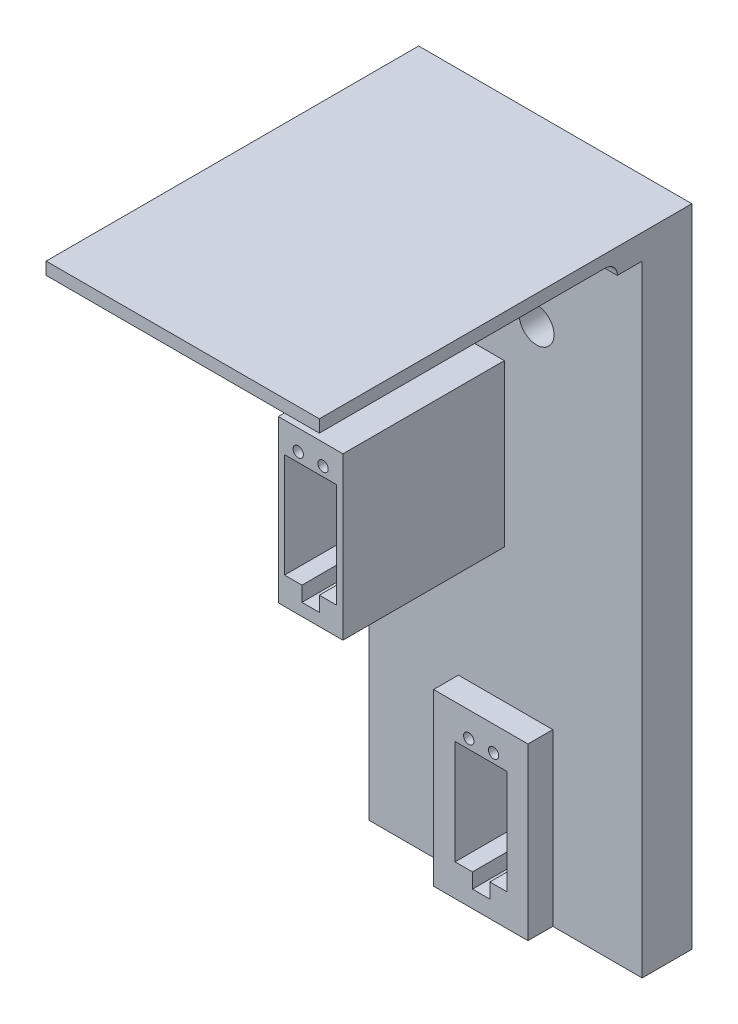
SolidWorks part; units mm, degrees
ref_plane "Front Plane" through (0, 0, 0) normal (0, 0, 1) x (1, 0, 0)
ref_plane "Top Plane" through (0, 0, 0) normal (0, 1, 0) x (1, 0, 0)
ref_plane "Right Plane" through (0, 0, 0) normal (1, 0, 0) x (0, 0, -1)
sketch "Sketch1" plane through (0, 0, 0) normal (0, 0, 1) x (1, 0, 0)
  line L1 (-75, 100) -> (75, 100)
  line L2 (-75, 100) -> (-75, -100)
  line L3 (-75, -100) -> (75, -100)
  line L4 (75, 100) -> (75, -100)
  line L5 (-75, 100) -> (75, -100) construction
  line L6 (-75, -100) -> (75, 100) construction
  point P0 (0, 0)
  dimension "D1" = 200
  dimension "D2" = 150
extrude "Boss-Extrude1" add sketch "Sketch1" along normal blind 30
sketch "Sketch2" plane through (0, 0, 30) normal (0, 0, 1) x (1, 0, 0)
  line L0 (75, -100) -> (75, 100) construction
  line L1 (-75, 100) -> (75, 100)
  line L2 (-75, 100) -> (-75, 95)
  line L3 (-75, 95) -> (75, 95)
  line L4 (75, 100) -> (75, 95)
  dimension "D1" = 5
extrude "Boss-Extrude2" add sketch "Sketch2" along normal blind 120
sketch "Sketch3" plane through (0, 0, 30) normal (0, 0, 1) x (1, 0, 0)
  line L0 (0, -100) -> (0, 0)
  line L1 (-75, -100) -> (75, -100) construction
  line L4 (0, 46.5) -> (0, 71.5)
  line L9 (-10.3251, 73.9819) -> (12.4051, 43.2014) construction
  line L10 (-12.4051, 43.2014) -> (10.3251, 73.9819) construction
  line L11 (-39.5, 13) -> (-39.5, 7)
  line L25 (-43, 13) -> (-36, 7) construction
  line L26 (-43, 7) -> (-36, 13) construction
  line L27 (-15.8, 46.5) -> (-12.5, 46.5)
  line L28 (-12.5, 46.5) -> (12.5, 46.5)
  line L29 (-12.5, 59) -> (12.5, 59)
  line L30 (12.5, 46.5) -> (-12.5, 46.5)
  line L31 (12.5, 46.5) -> (12.5, 71.5)
  line L32 (12.5, 71.5) -> (-12.5, 71.5)
  line L33 (-12.5, 46.5) -> (-12.5, 71.5)
  circle A0 centre (12.5, 46.5) radius 1.65
  circle A1 centre (-12.5, 46.5) radius 1.65
  circle A2 centre (12.5, 71.5) radius 1.65
  circle A3 centre (-12.5, 71.5) radius 1.65
  circle A4 centre (-12.5, 71.5) radius 3.3
  circle A5 centre (12.5, 71.5) radius 3.3
  circle A6 centre (12.5, 46.5) radius 3.3
  circle A7 centre (-12.5, 46.5) radius 3.3
  point P5 (0, 60)
  point P22 (-39.5, 10)
  dimension "D13" = 3.3
  dimension "D14" = 6.6
  dimension "D7" = 6
  dimension "D8" = 7
  dimension "D11" = 25
  dimension "D12" = 25
extrude "Cut-Extrude3" cut sketch "Sketch3" against normal blind 80 contours L11 | L11 | A1 L27 L33 | A1 L28 L27 | A1 L33 L28 | L31 A0 L30 | L30 A0 L31 | A2 L32 L31 | A2 L31 L32 | L32 A3 L33 | L33 A3 L32 region at (-12.5, 45.7997, 30) region at (-11.7997, 47.2003, 30) region at (11.7997, 47.2003, 30) region at (12.7334, 46.2666, 30) region at (-13.2003, 47.2003, 30) region at (-11.7997, 70.7997, 30) region at (-12.7334, 71.7334, 30) region at (12.7334, 71.7334, 30) region at (11.7997, 70.7997, 30)
ref_plane "Plane1" through (0, 0, 30) normal (0, 0, 1) x (1, 0, 0)
sketch "Sketch6" plane through (0, 0, 30) normal (0, 0, 1) x (1, 0, 0)
  circle A0 centre (-12.5, 71.5) radius 5
  circle A1 centre (12.5, 71.5) radius 5
  circle A2 centre (-12.5, 46.5) radius 5
  circle A3 centre (12.5, 46.5) radius 5
  dimension "D1" = 10
  dimension "D2" = 10
  dimension "D3" = 10
  dimension "D4" = 10
extrude "Cut-Extrude5" cut sketch "Sketch6" against normal blind 22
sketch "Sketch7" plane through (0, 0, 8) normal (0, 0, 1) x (1, 0, 0)
  circle A0 centre (-12.5, 71.5) radius 1.925
  circle A1 centre (12.5, 71.5) radius 1.925
  circle A2 centre (-12.5, 46.5) radius 1.925
  circle A3 centre (12.5, 46.5) radius 1.925
  dimension "D1" = 3.85
  dimension "D2" = 3.85
  dimension "D3" = 3.85
  dimension "D4" = 3.85
extrude "Cut-Extrude6" cut sketch "Sketch7" against normal blind 5
sketch "Sketch9" plane through (0, 0, 30) normal (0, 0, 1) x (1, 0, 0)
  line L0 (-12.5, 46.5) -> (12.5, 46.5)
  line L1 (12.5, 46.5) -> (0, 46.5)
  line L2 (0, 46.5) -> (1.1812, -69.9316)
  line L3 (1.1812, -69.9316) -> (1.1812, -115.5276)
  line L4 (-13.5, 15.5) -> (0.3145, 15.5)
  line L5 (-2.604, -89.8179) -> (4.396, -89.8179)
  line L6 (11.396, -83.8179) -> (11.396, -41.8179)
  line L7 (-2.604, -83.8179) -> (-9.604, -83.8179)
  line L8 (4.396, -89.8179) -> (4.396, -83.8179)
  line L9 (4.396, -83.8179) -> (11.396, -83.8179)
  line L10 (-9.604, -41.8179) -> (-9.604, -83.8179)
  line L11 (-24, 15.5) -> (-3, 15.5)
  line L12 (-17, -26.5) -> (-24, -26.5)
  line L18 (-24, 15.5) -> (-24, -26.5)
  line L19 (-10, -32.5) -> (-10, -26.5)
  line L20 (-17, -32.5) -> (-10, -32.5)
  line L21 (-17, -26.5) -> (-17, -32.5)
  line L22 (-10, -26.5) -> (-3, -26.5)
  line L23 (-3, -26.5) -> (-3, 15.5)
  line L24 (-9.604, -41.8179) -> (11.396, -41.8179)
  line L25 (-2.604, -83.8179) -> (-2.604, -89.8179)
  circle A6 centre (-8.5, 19.25) radius 2.08
  circle A7 centre (-18.5, 19.25) radius 2.08
  circle A8 centre (5.896, -38.0679) radius 2.08
  circle A9 centre (-4.104, -38.0679) radius 2.08
  point P16 (-39.5, 65.9329)
  dimension "D6" = 42
  dimension "D1" = 13.8145
fillet "Fillet1" radius 5 1 edges at (0, 95, 30)
extrude "Cut-Extrude7" cut sketch "Sketch9" against normal blind 30 contours L22 L23 L11 L18 L12 L21 L20 L19 | A7 | A6 region at (-13.5, -6.5909, 30) region at (-8.5, 19.25, 30) region at (-18.5, 19.25, 30)
sketch "Sketch10" plane through (0, 0, 30) normal (0, 0, 1) x (1, 0, 0)
  line L8 (0.1568, -105.1715) -> (0.1568, -105.1715)
  line L9 (8.2068, -105.9215) -> (-7.8932, -105.9215) construction
ref_plane "Plane2" through (0, 0, 0) normal (0, 0, -1) x (-1, 0, 0)
sketch "Sketch12" plane through (0, 0, 0) normal (0, 0, -1) x (-1, 0, 0)
  line L0 (13.5, 15.5) -> (13.5, -37.4614)
  line L1 (24, 15.5) -> (3, 15.5) construction
  line L2 (13.5, -37.4614) -> (26.5, -37.4614)
  line L3 (26.5, -37.4614) -> (26.5, 27.5386)
  line L4 (3, 15.5) -> (3, -26.5)
  line L5 (26.5, -37.4614) -> (0.5, -37.4614)
  line L6 (26.5, -37.4614) -> (26.5, 27.5386)
  line L7 (26.5, 27.5386) -> (0.5, 27.5386)
  line L8 (0.5, -37.4614) -> (0.5, 27.5386)
  line L9 (3, -26.5) -> (10, -26.5)
  line L10 (10, -26.5) -> (10, -32.5)
  line L11 (10, -32.5) -> (17, -32.5)
  line L12 (17, -32.5) -> (17, -26.5)
  line L13 (17, -26.5) -> (24, -26.5)
  line L14 (24, -26.5) -> (24, 15.5)
  line L15 (24, 15.5) -> (3, 15.5)
  circle A0 centre (8.5, 19.25) radius 2.08
  circle A1 centre (18.5, 19.25) radius 2.08
  dimension "D1" = 13
  dimension "D2" = 65
  dimension "D3" = 26
  dimension "D4" = 65
extrude "Boss-Extrude5" add sketch "Sketch12" against normal blind 85 contours L15 L14 L13 L12 L11 L2 L3 L7 L8 L5 L10 L9 L4 A1 A0 region at (-7, -36.7613, 0)
sketch "Sketch13" plane through (0, 0, 0) normal (0, 0, -1) x (-1, 0, 0)
  line L0 (-75, -100) -> (-75, -160)
  line L1 (-75, -160) -> (75, -160)
  line L2 (75, -160) -> (75, -100)
  line L3 (75, -100) -> (-75, -100) construction
  line L4 (75, -100) -> (-75, -100)
  dimension "D1" = 60
extrude "Boss-Extrude6" add sketch "Sketch13" against normal blind 30
sketch "Sketch15" plane through (0, 0, 30) normal (0, 0, 1) x (1, 0, 0)
  line L0 (-10.3432, -105.1715) -> (10.6568, -105.1715)
  line L1 (10.6568, -105.1715) -> (10.6568, -147.1715)
  line L2 (10.6568, -147.1715) -> (3.6568, -147.1715)
  line L3 (3.6568, -147.1715) -> (3.6568, -153.1715)
  line L4 (3.6568, -153.1715) -> (-3.3432, -153.1715)
  line L5 (-3.3432, -153.1715) -> (-3.3432, -147.1715)
  line L6 (-3.3432, -147.1715) -> (-10.3432, -147.1715)
  line L7 (-10.3432, -147.1715) -> (-10.3432, -105.1715)
  circle A0 centre (-4.8432, -101.4215) radius 2.08
  circle A1 centre (5.1568, -101.4215) radius 2.08
  dimension "D1" = 4.16
  dimension "D2" = 4.16
extrude "Cut-Extrude8" cut sketch "Sketch15" against normal blind 30
sketch "Sketch16" plane through (0, 0, 30) normal (0, 0, 1) x (1, 0, 0)
  circle A0 centre (-12.5, 71.5) radius 7
  circle A1 centre (12.5, 71.5) radius 7
  circle A2 centre (12.5, 46.5) radius 7
  circle A3 centre (-12.5, 46.5) radius 7
  dimension "D1" = 14
extrude "Cut-Extrude9" cut sketch "Sketch16" against normal blind 22
sketch "Sketch17" plane through (0, 0, 0) normal (0, 0, -1) x (-1, 0, 0)
  line L0 (-75, -160) -> (75, -160) construction
  line L1 (75, 100) -> (55, 100)
  line L2 (75, 100) -> (75, -160)
  line L3 (75, -160) -> (55, -160)
  line L4 (55, 100) -> (55, -160)
  line L5 (-55, -160) -> (-75, -160)
  line L6 (-75, 100) -> (-75, -160)
  line L7 (-55, 100) -> (-75, 100)
  line L8 (-55, 100) -> (-55, -160)
  dimension "D1" = 20
extrude "Cut-Extrude10" cut sketch "Sketch17" against normal blind 150
sketch "Sketch19" plane through (0, 0, 30) normal (0, 0, 1) x (1, 0, 0)
  line L0 (-55, 90) -> (55, 90)
  line L1 (55, 90) -> (55, -160)
  line L2 (55, -160) -> (19, -160)
  line L3 (55, -160) -> (-55, -160) construction
  line L4 (19, -160) -> (19, -91.3882)
  line L5 (19, -91.3882) -> (-19, -91.3882)
  line L6 (-19, -91.3882) -> (-19, -160)
  line L7 (-19, -160) -> (-55, -160)
  line L8 (-55, -160) -> (-55, 90)
  line L9 (-26.5, 27.5386) -> (-26.5, -37.4614)
  line L10 (-26.5, -37.4614) -> (-0.5, -37.4614) construction
  line L11 (-26.5, 27.5386) -> (-26.5, -37.4614) construction
  line L12 (-26.5, -37.4614) -> (-0.5, -37.4614)
  line L13 (-0.5, -37.4614) -> (-0.5, 27.5386)
  line L14 (-0.5, 27.5386) -> (-26.5, 27.5386)
  dimension "D1" = 36
  dimension "D2" = 36
extrude "Cut-Extrude11" cut sketch "Sketch19" against normal blind 10
